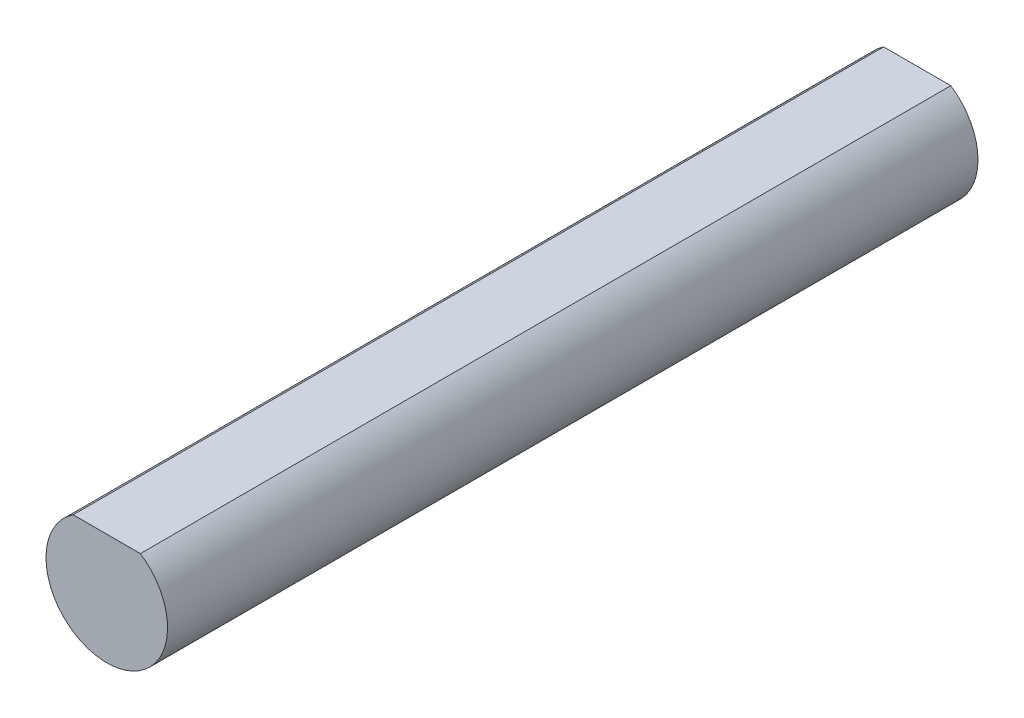
SolidWorks part; units mm, degrees
material "Cast Alloy Steel"
ref_plane "Front Plane" through (0, 0, 0) normal (0, 0, 1) x (1, 0, 0)
ref_plane "Top Plane" through (0, 0, 0) normal (0, 1, 0) x (1, 0, 0)
ref_plane "Right Plane" through (0, 0, 0) normal (1, 0, 0) x (0, 0, -1)
sketch "Sketch1" plane through (0, 0, 0) normal (0, 0, 1) x (1, 0, 0)
  line L0 (-1.6583, 2.5) -> (1.6583, 2.5)
  arc A0 (-1.6583, 2.5) -> (1.6583, 2.5) centre (0, 0) ccw
  dimension "D2" = 6
  dimension "D1" = 2.5
extrude "Boss-Extrude1" add sketch "Sketch1" along normal blind 40
ref_axis "Axis1" through (0, 0, 40) along (0, 0, -1)
